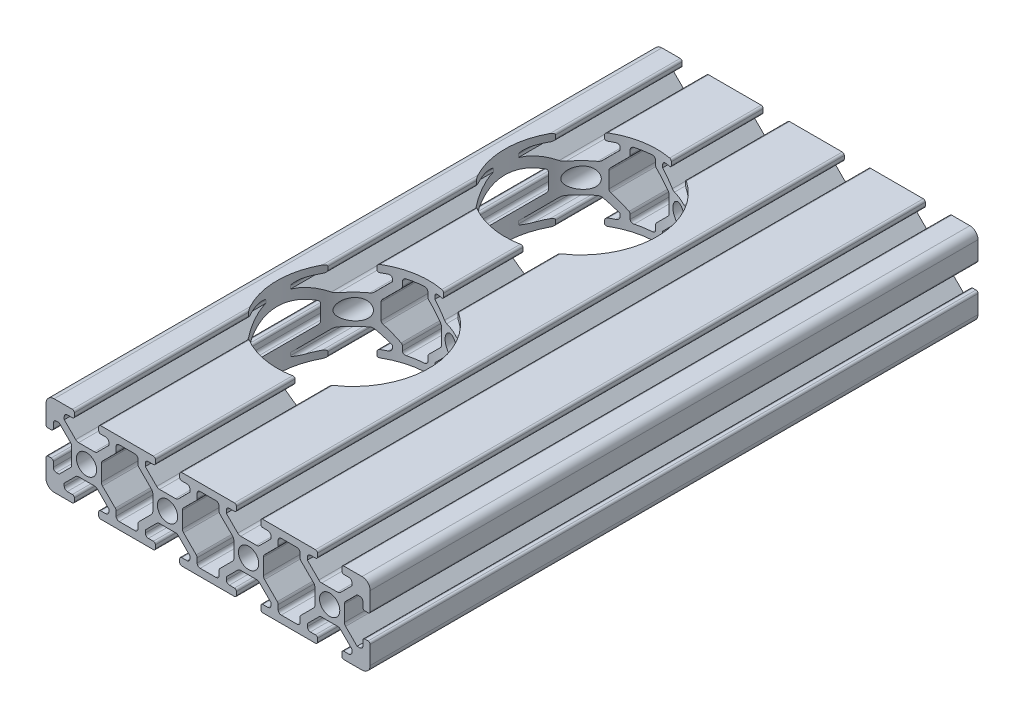
SolidWorks part; units mm, degrees
material "6063-T5"
ref_plane "Front Plane" through (0, 0, 0) normal (0, 0, 1) x (1, 0, 0)
ref_plane "Top Plane" through (0, 0, 0) normal (0, 1, 0) x (1, 0, 0)
ref_plane "Right Plane" through (0, 0, 0) normal (1, 0, 0) x (0, 0, -1)
sketch "Sketch1" plane through (0, 0, 0) normal (0, 0, 1) x (1, 0, 0)
  line L0 (-41.935, 2.3415) -> (-37.435, 2.3415)
  line L1 (36.065, 4.3415) -> (36.065, 8.8415)
  line L2 (34.065, 22.3415) -> (29.565, 22.3415)
  line L3 (-43.935, 20.3415) -> (-43.935, 15.8415)
  line L4 (-10.935, 21.8415) -> (-10.935, 21.0415)
  line L5 (-16.935, 21.8415) -> (-16.935, 21.0415)
  line L6 (-36.935, 21.8415) -> (-36.935, 21.0415)
  line L7 (-30.935, 21.8415) -> (-30.935, 21.0415)
  line L8 (-37.435, 22.3415) -> (-41.935, 22.3415)
  line L9 (9.065, 21.8415) -> (9.065, 21.0415)
  line L10 (3.065, 21.8415) -> (3.065, 21.0415)
  line L11 (29.065, 21.8415) -> (29.065, 21.0415)
  line L12 (23.065, 21.8415) -> (23.065, 21.0415)
  line L13 (-10.935, 3.6415) -> (-10.935, 2.8415)
  line L14 (-16.935, 3.6415) -> (-16.935, 2.8415)
  line L15 (9.065, 3.6415) -> (9.065, 2.8415)
  line L16 (3.065, 3.6415) -> (3.065, 2.8415)
  line L17 (29.065, 3.6415) -> (29.065, 2.8415)
  line L18 (23.065, 3.6415) -> (23.065, 2.8415)
  line L19 (-30.935, 3.6415) -> (-30.935, 2.8415)
  line L20 (-36.935, 3.6415) -> (-36.935, 2.8415)
  line L21 (-30.435, 22.3415) -> (-17.435, 22.3415) construction
  line L22 (-17.435, 22.3415) -> (-30.435, 22.3415)
  line L23 (2.565, 22.3415) -> (-10.435, 22.3415)
  line L24 (22.565, 22.3415) -> (9.565, 22.3415)
  line L25 (29.565, 2.3415) -> (34.065, 2.3415)
  line L26 (9.565, 2.3415) -> (22.565, 2.3415)
  line L27 (-10.435, 2.3415) -> (2.565, 2.3415)
  line L28 (-30.435, 2.3415) -> (-17.435, 2.3415)
  line L29 (35.565, 15.3415) -> (34.765, 15.3415)
  line L30 (35.565, 9.3415) -> (34.765, 9.3415)
  line L31 (-43.435, 15.3415) -> (-42.635, 15.3415)
  line L32 (-43.435, 9.3415) -> (-42.635, 9.3415)
  line L33 (-43.935, 8.8415) -> (-43.935, 4.3415)
  line L34 (36.065, 15.8415) -> (36.065, 20.3415)
  line L35 (-42.135, 15.8415) -> (-42.135, 17.0915)
  line L36 (-38.685, 20.5415) -> (-37.435, 20.5415)
  line L37 (34.265, 17.0915) -> (34.265, 15.8415)
  line L38 (30.815, 4.1415) -> (29.565, 4.1415)
  line L39 (-42.135, 7.5915) -> (-42.135, 8.8415)
  line L40 (-30.435, 20.5415) -> (-29.185, 20.5415)
  line L41 (-37.435, 4.1415) -> (-38.685, 4.1415)
  line L42 (-10.435, 20.5415) -> (-9.185, 20.5415)
  line L43 (-17.435, 4.1415) -> (-18.685, 4.1415)
  line L44 (9.565, 20.5415) -> (10.815, 20.5415)
  line L45 (2.565, 4.1415) -> (1.315, 4.1415)
  line L46 (29.565, 20.5415) -> (30.815, 20.5415)
  line L47 (22.565, 4.1415) -> (21.315, 4.1415)
  line L48 (34.265, 8.8415) -> (34.265, 7.5915)
  line L49 (-31.2649, 16.2843) -> (-28.435, 19.1142)
  line L50 (-31.2649, 8.3986) -> (-28.435, 5.5687)
  line L51 (-11.2649, 16.2843) -> (-8.435, 19.1142)
  line L52 (-9.9921, 15.0116) -> (-6.8546, 18.149)
  line L53 (-16.6051, 16.2843) -> (-19.435, 19.1142)
  line L54 (-21.0153, 18.149) -> (-17.8778, 15.0116)
  line L55 (-16.6051, 8.3986) -> (-19.435, 5.5687)
  line L56 (-21.0153, 6.5339) -> (-17.8778, 9.6714)
  line L57 (3.3949, 16.2843) -> (0.565, 19.1142)
  line L58 (-1.0153, 18.149) -> (2.1222, 15.0116)
  line L59 (3.3949, 8.3986) -> (0.565, 5.5687)
  line L60 (-1.0153, 6.5339) -> (2.1222, 9.6714)
  line L61 (23.3949, 16.2843) -> (20.565, 19.1142)
  line L62 (18.9847, 18.149) -> (22.1222, 15.0116)
  line L63 (23.3949, 8.3986) -> (20.565, 5.5687)
  line L64 (18.9847, 6.5339) -> (22.1222, 9.6714)
  line L65 (-9.9921, 9.6714) -> (-6.8546, 6.5339)
  line L66 (-29.9921, 15.0116) -> (-26.8546, 18.149)
  line L67 (-37.8778, 9.6714) -> (-40.7077, 6.8415)
  line L68 (-36.6051, 8.3986) -> (-39.435, 5.5687)
  line L69 (-36.6051, 16.2843) -> (-39.435, 19.1142)
  line L70 (-11.2649, 8.3986) -> (-8.435, 5.5687)
  line L71 (-29.9921, 9.6714) -> (-26.8546, 6.5339)
  line L72 (8.7351, 16.2843) -> (11.565, 19.1142)
  line L73 (-37.8778, 15.0116) -> (-40.7077, 17.8415)
  line L74 (10.0079, 15.0116) -> (13.1454, 18.149)
  line L75 (10.0079, 9.6714) -> (13.1454, 6.5339)
  line L76 (8.7351, 8.3986) -> (11.565, 5.5687)
  line L77 (28.7351, 16.2843) -> (31.565, 19.1142)
  line L78 (30.0079, 15.0116) -> (32.8378, 17.8415)
  line L79 (30.0079, 9.6714) -> (32.8378, 6.8415)
  line L80 (28.7351, 8.3986) -> (31.565, 5.5687)
  line L81 (-15.898, 15.9915) -> (-11.972, 15.9915)
  line L82 (-25.885, 20.5415) -> (-21.985, 20.5415)
  line L83 (-29.185, 4.1415) -> (-30.435, 4.1415)
  line L84 (-28.435, 19.7915) -> (-28.435, 19.1142)
  line L85 (-9.185, 4.1415) -> (-10.435, 4.1415)
  line L86 (-39.435, 19.7915) -> (-39.435, 19.1142)
  line L87 (10.815, 4.1415) -> (9.565, 4.1415)
  line L88 (-19.435, 19.7915) -> (-19.435, 19.1142)
  line L89 (-18.685, 20.5415) -> (-17.435, 20.5415)
  line L90 (1.315, 20.5415) -> (2.565, 20.5415)
  line L91 (-10.285, 14.3044) -> (-10.285, 10.3785)
  line L92 (-11.972, 8.6915) -> (-15.898, 8.6915)
  line L93 (-17.585, 10.3785) -> (-17.585, 14.3044)
  line L94 (21.315, 20.5415) -> (22.565, 20.5415)
  line L95 (0.565, 19.7915) -> (0.565, 19.1142)
  line L96 (-8.435, 19.7915) -> (-8.435, 19.1142)
  line L97 (-30.285, 14.3044) -> (-30.285, 10.3785)
  line L98 (-31.972, 8.6915) -> (-35.898, 8.6915)
  line L99 (-37.585, 10.3785) -> (-37.585, 14.3044)
  line L100 (-35.898, 15.9915) -> (-31.972, 15.9915)
  line L101 (4.102, 15.9915) -> (8.028, 15.9915)
  line L102 (9.715, 14.3044) -> (9.715, 10.3785)
  line L103 (8.028, 8.6915) -> (4.102, 8.6915)
  line L104 (2.415, 10.3785) -> (2.415, 14.3044)
  line L105 (24.102, 15.9915) -> (28.028, 15.9915)
  line L106 (29.715, 14.3044) -> (29.715, 10.3785)
  line L107 (28.028, 8.6915) -> (24.102, 8.6915)
  line L108 (22.415, 10.3785) -> (22.415, 14.3044)
  line L109 (20.565, 19.7915) -> (20.565, 19.1142)
  line L110 (11.565, 19.7915) -> (11.565, 19.1142)
  line L111 (-39.435, 4.8915) -> (-39.435, 5.5687)
  line L112 (31.565, 19.7915) -> (31.565, 19.1142)
  line L113 (-19.435, 4.8915) -> (-19.435, 5.5687)
  line L114 (-28.435, 4.8915) -> (-28.435, 5.5687)
  line L115 (0.565, 4.8915) -> (0.565, 5.5687)
  line L116 (-8.435, 4.8915) -> (-8.435, 5.5687)
  line L117 (20.565, 4.8915) -> (20.565, 5.5687)
  line L118 (11.565, 4.8915) -> (11.565, 5.5687)
  line L119 (-41.385, 17.8415) -> (-40.7077, 17.8415)
  line L120 (31.565, 4.8915) -> (31.565, 5.5687)
  line L121 (-41.385, 6.8415) -> (-40.7077, 6.8415)
  line L122 (33.515, 17.8415) -> (32.8378, 17.8415)
  line L123 (-26.635, 19.7915) -> (-26.635, 18.6793)
  line L124 (33.515, 6.8415) -> (32.8378, 6.8415)
  line L125 (-21.235, 19.7915) -> (-21.235, 18.6793)
  line L126 (-5.885, 20.5415) -> (-1.985, 20.5415)
  line L127 (-6.635, 19.7915) -> (-6.635, 18.6793)
  line L128 (-1.235, 19.7915) -> (-1.235, 18.6793)
  line L129 (14.115, 20.5415) -> (18.015, 20.5415)
  line L130 (13.365, 19.7915) -> (13.365, 18.6793)
  line L131 (18.765, 19.7915) -> (18.765, 18.6793)
  line L132 (-26.635, 6.0036) -> (-26.635, 4.8915)
  line L133 (-25.885, 4.1415) -> (-21.985, 4.1415)
  line L134 (-21.235, 4.8915) -> (-21.235, 6.0036)
  line L135 (-6.635, 6.0036) -> (-6.635, 4.8915)
  line L136 (-5.885, 4.1415) -> (-1.985, 4.1415)
  line L137 (-1.235, 4.8915) -> (-1.235, 6.0036)
  line L138 (13.365, 6.0036) -> (13.365, 4.8915)
  line L139 (14.115, 4.1415) -> (18.015, 4.1415)
  line L140 (18.765, 4.8915) -> (18.765, 6.0036)
  circle A0 centre (-33.935, 12.3415) radius 2.5
  circle A1 centre (-13.935, 12.3415) radius 2.5
  circle A2 centre (6.065, 12.3415) radius 2.5
  circle A3 centre (26.065, 12.3415) radius 2.5
  arc A4 (34.065, 2.3415) -> (36.065, 4.3415) centre (34.065, 4.3415) ccw
  arc A5 (36.065, 20.3415) -> (34.065, 22.3415) centre (34.065, 20.3415) ccw
  arc A6 (-41.935, 2.3415) -> (-43.935, 4.3415) centre (-41.935, 4.3415) cw
  arc A7 (-41.935, 22.3415) -> (-43.935, 20.3415) centre (-41.935, 20.3415) ccw
  arc A8 (-31.2649, 16.2843) -> (-31.972, 15.9915) centre (-31.972, 16.9915) cw
  arc A9 (-36.6051, 16.2843) -> (-35.898, 15.9915) centre (-35.898, 16.9915) ccw
  arc A10 (-37.8778, 15.0116) -> (-37.585, 14.3044) centre (-38.585, 14.3044) cw
  arc A11 (-37.8778, 9.6714) -> (-37.585, 10.3785) centre (-38.585, 10.3785) ccw
  arc A12 (-36.6051, 8.3986) -> (-35.898, 8.6915) centre (-35.898, 7.6915) cw
  arc A13 (-31.2649, 8.3986) -> (-31.972, 8.6915) centre (-31.972, 7.6915) ccw
  arc A14 (-11.2649, 8.3986) -> (-11.972, 8.6915) centre (-11.972, 7.6915) ccw
  arc A15 (-16.6051, 8.3986) -> (-15.898, 8.6915) centre (-15.898, 7.6915) cw
  arc A16 (-16.6051, 16.2843) -> (-15.898, 15.9915) centre (-15.898, 16.9915) ccw
  arc A17 (-11.2649, 16.2843) -> (-11.972, 15.9915) centre (-11.972, 16.9915) cw
  arc A18 (3.3949, 8.3986) -> (4.102, 8.6915) centre (4.102, 7.6915) cw
  arc A19 (8.7351, 8.3986) -> (8.028, 8.6915) centre (8.028, 7.6915) ccw
  arc A20 (8.7351, 16.2843) -> (8.028, 15.9915) centre (8.028, 16.9915) cw
  arc A21 (3.3949, 16.2843) -> (4.102, 15.9915) centre (4.102, 16.9915) ccw
  arc A22 (28.7351, 16.2843) -> (28.028, 15.9915) centre (28.028, 16.9915) cw
  arc A23 (23.3949, 16.2843) -> (24.102, 15.9915) centre (24.102, 16.9915) ccw
  arc A24 (23.3949, 8.3986) -> (24.102, 8.6915) centre (24.102, 7.6915) cw
  arc A25 (28.7351, 8.3986) -> (28.028, 8.6915) centre (28.028, 7.6915) ccw
  arc A26 (30.0079, 9.6714) -> (29.715, 10.3785) centre (30.715, 10.3785) cw
  arc A27 (30.0079, 15.0116) -> (29.715, 14.3044) centre (30.715, 14.3044) ccw
  arc A28 (22.1222, 9.6714) -> (22.415, 10.3785) centre (21.415, 10.3785) ccw
  arc A29 (22.1222, 15.0116) -> (22.415, 14.3044) centre (21.415, 14.3044) cw
  arc A30 (10.0079, 9.6714) -> (9.715, 10.3785) centre (10.715, 10.3785) cw
  arc A31 (10.0079, 15.0116) -> (9.715, 14.3044) centre (10.715, 14.3044) ccw
  arc A32 (34.265, 17.0915) -> (33.515, 17.8415) centre (33.515, 17.0915) ccw
  arc A33 (31.565, 19.7915) -> (30.815, 20.5415) centre (30.815, 19.7915) ccw
  arc A34 (34.265, 7.5915) -> (33.515, 6.8415) centre (33.515, 7.5915) cw
  arc A35 (31.565, 4.8915) -> (30.815, 4.1415) centre (30.815, 4.8915) cw
  arc A36 (2.1222, 9.6714) -> (2.415, 10.3785) centre (1.415, 10.3785) ccw
  arc A37 (2.1222, 15.0116) -> (2.415, 14.3044) centre (1.415, 14.3044) cw
  arc A38 (-9.9921, 9.6714) -> (-10.285, 10.3785) centre (-9.285, 10.3785) cw
  arc A39 (-9.9921, 15.0116) -> (-10.285, 14.3044) centre (-9.285, 14.3044) ccw
  arc A40 (-29.9921, 15.0116) -> (-30.285, 14.3044) centre (-29.285, 14.3044) ccw
  arc A41 (-29.9921, 9.6714) -> (-30.285, 10.3785) centre (-29.285, 10.3785) cw
  arc A42 (-17.8778, 9.6714) -> (-17.585, 10.3785) centre (-18.585, 10.3785) ccw
  arc A43 (-17.8778, 15.0116) -> (-17.585, 14.3044) centre (-18.585, 14.3044) cw
  arc A44 (21.315, 4.1415) -> (20.565, 4.8915) centre (21.315, 4.8915) cw
  arc A45 (18.015, 4.1415) -> (18.765, 4.8915) centre (18.015, 4.8915) ccw
  arc A46 (13.365, 4.8915) -> (14.115, 4.1415) centre (14.115, 4.8915) ccw
  arc A47 (10.815, 4.1415) -> (11.565, 4.8915) centre (10.815, 4.8915) ccw
  arc A48 (1.315, 4.1415) -> (0.565, 4.8915) centre (1.315, 4.8915) cw
  arc A49 (20.565, 19.7915) -> (21.315, 20.5415) centre (21.315, 19.7915) cw
  arc A50 (18.015, 20.5415) -> (18.765, 19.7915) centre (18.015, 19.7915) cw
  arc A51 (14.115, 20.5415) -> (13.365, 19.7915) centre (14.115, 19.7915) ccw
  arc A52 (9.065, 21.0415) -> (9.565, 20.5415) centre (9.565, 21.0415) ccw
  arc A53 (9.065, 21.8415) -> (9.565, 22.3415) centre (9.565, 21.8415) cw
  arc A54 (23.065, 21.0415) -> (22.565, 20.5415) centre (22.565, 21.0415) cw
  arc A55 (23.065, 21.8415) -> (22.565, 22.3415) centre (22.565, 21.8415) ccw
  arc A56 (29.065, 21.0415) -> (29.565, 20.5415) centre (29.565, 21.0415) ccw
  arc A57 (29.065, 21.8415) -> (29.565, 22.3415) centre (29.565, 21.8415) cw
  arc A58 (34.765, 15.3415) -> (34.265, 15.8415) centre (34.765, 15.8415) cw
  arc A59 (35.565, 15.3415) -> (36.065, 15.8415) centre (35.565, 15.8415) ccw
  arc A60 (34.765, 9.3415) -> (34.265, 8.8415) centre (34.765, 8.8415) ccw
  arc A61 (35.565, 9.3415) -> (36.065, 8.8415) centre (35.565, 8.8415) cw
  arc A62 (29.065, 2.8415) -> (29.565, 2.3415) centre (29.565, 2.8415) ccw
  arc A63 (29.065, 3.6415) -> (29.565, 4.1415) centre (29.565, 3.6415) cw
  arc A64 (23.065, 2.8415) -> (22.565, 2.3415) centre (22.565, 2.8415) cw
  arc A65 (23.065, 3.6415) -> (22.565, 4.1415) centre (22.565, 3.6415) ccw
  arc A66 (9.065, 2.8415) -> (9.565, 2.3415) centre (9.565, 2.8415) ccw
  arc A67 (9.065, 3.6415) -> (9.565, 4.1415) centre (9.565, 3.6415) cw
  arc A68 (3.065, 2.8415) -> (2.565, 2.3415) centre (2.565, 2.8415) cw
  arc A69 (3.065, 3.6415) -> (2.565, 4.1415) centre (2.565, 3.6415) ccw
  arc A70 (-10.935, 2.8415) -> (-10.435, 2.3415) centre (-10.435, 2.8415) ccw
  arc A71 (-10.935, 3.6415) -> (-10.435, 4.1415) centre (-10.435, 3.6415) cw
  arc A72 (-16.935, 2.8415) -> (-17.435, 2.3415) centre (-17.435, 2.8415) cw
  arc A73 (-16.935, 3.6415) -> (-17.435, 4.1415) centre (-17.435, 3.6415) ccw
  arc A74 (3.065, 21.0415) -> (2.565, 20.5415) centre (2.565, 21.0415) cw
  arc A75 (3.065, 21.8415) -> (2.565, 22.3415) centre (2.565, 21.8415) ccw
  arc A76 (-10.935, 21.0415) -> (-10.435, 20.5415) centre (-10.435, 21.0415) ccw
  arc A77 (-10.935, 21.8415) -> (-10.435, 22.3415) centre (-10.435, 21.8415) cw
  arc A78 (-16.935, 21.0415) -> (-17.435, 20.5415) centre (-17.435, 21.0415) cw
  arc A79 (-16.935, 21.8415) -> (-17.435, 22.3415) centre (-17.435, 21.8415) ccw
  arc A80 (-30.935, 21.0415) -> (-30.435, 20.5415) centre (-30.435, 21.0415) ccw
  arc A81 (-30.435, 22.3415) -> (-30.935, 21.8415) centre (-30.435, 21.8415) ccw
  arc A82 (-30.935, 2.8415) -> (-30.435, 2.3415) centre (-30.435, 2.8415) ccw
  arc A83 (-30.935, 3.6415) -> (-30.435, 4.1415) centre (-30.435, 3.6415) cw
  arc A84 (-36.935, 2.8415) -> (-37.435, 2.3415) centre (-37.435, 2.8415) cw
  arc A85 (-36.935, 3.6415) -> (-37.435, 4.1415) centre (-37.435, 3.6415) ccw
  arc A86 (-43.935, 8.8415) -> (-43.435, 9.3415) centre (-43.435, 8.8415) cw
  arc A87 (-42.635, 9.3415) -> (-42.135, 8.8415) centre (-42.635, 8.8415) cw
  arc A88 (-43.935, 15.8415) -> (-43.435, 15.3415) centre (-43.435, 15.8415) ccw
  arc A89 (-42.635, 15.3415) -> (-42.135, 15.8415) centre (-42.635, 15.8415) ccw
  arc A90 (-37.435, 22.3415) -> (-36.935, 21.8415) centre (-37.435, 21.8415) cw
  arc A91 (-36.935, 21.0415) -> (-37.435, 20.5415) centre (-37.435, 21.0415) cw
  arc A92 (11.565, 19.7915) -> (10.815, 20.5415) centre (10.815, 19.7915) ccw
  arc A93 (0.565, 19.7915) -> (1.315, 20.5415) centre (1.315, 19.7915) cw
  arc A94 (-6.635, 4.8915) -> (-5.885, 4.1415) centre (-5.885, 4.8915) ccw
  arc A95 (-5.885, 20.5415) -> (-6.635, 19.7915) centre (-5.885, 19.7915) ccw
  arc A96 (-1.985, 20.5415) -> (-1.235, 19.7915) centre (-1.985, 19.7915) cw
  arc A97 (-1.985, 4.1415) -> (-1.235, 4.8915) centre (-1.985, 4.8915) ccw
  arc A98 (-9.185, 4.1415) -> (-8.435, 4.8915) centre (-9.185, 4.8915) ccw
  arc A99 (-18.685, 4.1415) -> (-19.435, 4.8915) centre (-18.685, 4.8915) cw
  arc A100 (-29.185, 4.1415) -> (-28.435, 4.8915) centre (-29.185, 4.8915) ccw
  arc A101 (-38.685, 4.1415) -> (-39.435, 4.8915) centre (-38.685, 4.8915) cw
  arc A102 (-41.385, 6.8415) -> (-42.135, 7.5915) centre (-41.385, 7.5915) cw
  arc A103 (-42.135, 17.0915) -> (-41.385, 17.8415) centre (-41.385, 17.0915) cw
  arc A104 (-19.435, 19.7915) -> (-18.685, 20.5415) centre (-18.685, 19.7915) cw
  arc A105 (-9.185, 20.5415) -> (-8.435, 19.7915) centre (-9.185, 19.7915) cw
  arc A106 (-21.985, 20.5415) -> (-21.235, 19.7915) centre (-21.985, 19.7915) cw
  arc A107 (-25.885, 20.5415) -> (-26.635, 19.7915) centre (-25.885, 19.7915) ccw
  arc A108 (-28.435, 19.7915) -> (-29.185, 20.5415) centre (-29.185, 19.7915) ccw
  arc A109 (-38.685, 20.5415) -> (-39.435, 19.7915) centre (-38.685, 19.7915) ccw
  arc A110 (18.765, 6.0036) -> (18.9847, 6.5339) centre (19.515, 6.0036) cw
  arc A111 (13.365, 6.0036) -> (13.1454, 6.5339) centre (12.615, 6.0036) ccw
  arc A112 (18.765, 18.6793) -> (18.9847, 18.149) centre (19.515, 18.6793) ccw
  arc A113 (13.365, 18.6793) -> (13.1454, 18.149) centre (12.615, 18.6793) cw
  arc A114 (-1.235, 6.0036) -> (-1.0153, 6.5339) centre (-0.485, 6.0036) cw
  arc A115 (-6.635, 6.0036) -> (-6.8546, 6.5339) centre (-7.385, 6.0036) ccw
  arc A116 (-1.235, 18.6793) -> (-1.0153, 18.149) centre (-0.485, 18.6793) ccw
  arc A117 (-6.635, 18.6793) -> (-6.8546, 18.149) centre (-7.385, 18.6793) cw
  arc A118 (-21.235, 18.6793) -> (-21.0153, 18.149) centre (-20.485, 18.6793) ccw
  arc A119 (-26.635, 18.6793) -> (-26.8546, 18.149) centre (-27.385, 18.6793) cw
  arc A120 (-26.635, 6.0036) -> (-26.8546, 6.5339) centre (-27.385, 6.0036) ccw
  arc A121 (-21.235, 6.0036) -> (-21.0153, 6.5339) centre (-20.485, 6.0036) cw
  arc A122 (-21.985, 4.1415) -> (-21.235, 4.8915) centre (-21.985, 4.8915) ccw
  arc A123 (-26.635, 4.8915) -> (-25.885, 4.1415) centre (-25.885, 4.8915) ccw
extrude "Boss-Extrude1" add sketch "Sketch1" along normal blind 150
sketch "Sketch2" plane through (0, 22.3415, 0) normal (0, 1, 0) x (1, 0, 0)
  line L0 (-17.435, 0) -> (-30.435, 0) construction
  line L3 (-43.935, -150) -> (-43.935, 0) construction
  circle A0 centre (-20.935, -41) radius 18.75
  circle A1 centre (-20.935, -97.216) radius 18.75
  point P8 (-43.935, -48.2518)
  point P9 (0, 0)
  dimension "D4" = 37.5
  dimension "D1" = 41
  dimension "D2" = 23
  dimension "D3" = 56.216
extrude "Cut-Extrude1" cut sketch "Sketch2" against normal through all
